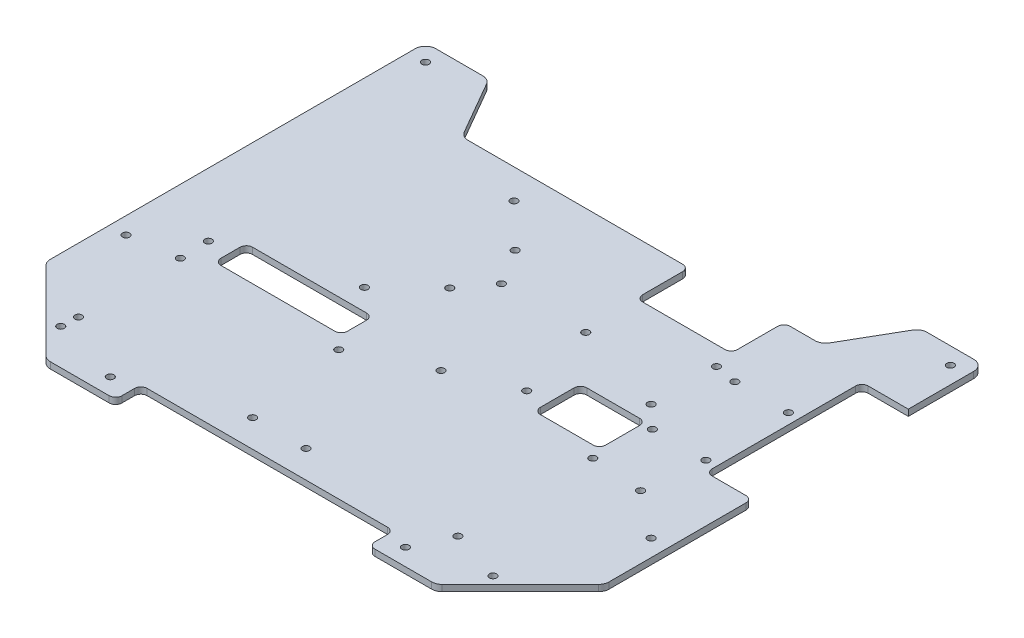
SolidWorks part; units mm, degrees
material "Acier non allié"
ref_plane "Front" through (0, 0, 0) normal (0, 0, 1) x (1, 0, 0)
ref_plane "Top" through (0, 0, 0) normal (0, 1, 0) x (1, 0, 0)
ref_plane "Right" through (0, 0, 0) normal (1, 0, 0) x (0, 0, -1)
sketch "Esquisse1" plane through (0, 0, 0) normal (0, 1, 0) x (1, 0, 0)
  line L0 (0, 0) -> (0, 190) construction
  line L1 (-92.5, 0) -> (92.5, 0)
  line L2 (92.5, 0) -> (132.5, 40)
  line L3 (132.5, 40) -> (132.5, 220)
  line L4 (132.5, 220) -> (102.5, 220)
  line L5 (102.5, 220) -> (85.1795, 190)
  line L6 (85.1795, 190) -> (-85.1795, 190)
  line L7 (-102.5, 220) -> (-85.1795, 190)
  line L8 (-132.5, 220) -> (-102.5, 220)
  line L9 (-132.5, 40) -> (-132.5, 220)
  line L10 (-92.5, 0) -> (-132.5, 40)
  dimension "D1" = 132.5
  dimension "D2" = 220
  dimension "D3" = 60
  dimension "D4" = 30
  dimension "D5" = 40
  dimension "D6" = 40
  dimension "D7" = 30
extrude "Boss.-Extru.1" add sketch "Esquisse1" along normal blind 3
fillet "Congé1" radius 5 10 edges at (92.5, 1.5, 0) (132.5, 1.5, -40) (132.5, 1.5, -220) (102.5, 1.5, -220) (85.1795, 1.5, -190) (-85.1795, 1.5, -190) (-102.5, 1.5, -220) (-132.5, 1.5, -220) (-92.5, 1.5, 0) (-132.5, 1.5, -40)
sketch "Esquisse2" plane through (0, 3, 0) normal (0, 1, 0) x (1, 0, 0)
  line L0 (0, 0) -> (0, 294.1173) construction
  line L2 (-90.4289, 0) -> (90.4289, 0) construction
  circle A0 centre (70, 8) radius 1
  circle A1 centre (124.5, 70) radius 1
  circle A2 centre (124.5, 212) radius 1
  circle A3 centre (-124.5, 212) radius 1
  circle A4 centre (-124.5, 70) radius 1
  circle A5 centre (-70, 8) radius 1
  dimension "D2" = 2
  dimension "D6" = 2
  dimension "D9" = 2
  dimension "D1" = 70
  dimension "D3" = 8
  dimension "D4" = 124.5
  dimension "D5" = 70
  dimension "D7" = 124.5
  dimension "D8" = 212
extrude "Enlèv. mat.-Extru.1" cut sketch "Esquisse2" against normal blind 3
hole_wizard "Dégagement M31" positions "Esquisse3" profile "Esquisse4" hole size "M3" standard "ISO" end condition through all
sketch "Esquisse3" plane through (0, 3, 0) normal (0, 1, 0) x (1, 0, 0)
  point P0 (70, 8)
  point P3 (-70, 8)
  point P6 (-124.5, 70)
  point P9 (-124.5, 212)
  point P12 (124.5, 212)
  point P15 (124.5, 70)
sketch "Esquisse4" plane through (70, 3, -8) normal (1, 0, 0) x (0, 0, 1)
  line L0 (0, 0) -> (0, 3)
  line L1 (0, 3) -> (1.7, 3)
  line L2 (1.7, 3) -> (1.7, 0)
  line L5 (1.7, 0) -> (0, 0)
  line L11 (0, -6.35) -> (0, 107.95) construction
  dimension "Diamètre du perçage jusqu'au prochain" = 3.4
  dimension "Profondeur du perçage jusqu'au prochain" = 3
sketch "Esquisse5" plane through (0, 3, 0) normal (0, 1, 0) x (1, 0, 0)
  line L0 (82.2927, 190) -> (-82.2927, 190) construction
  line L1 (67.5, 190) -> (22.5, 190)
  line L2 (67.5, 190) -> (67.5, 165)
  line L3 (67.5, 165) -> (22.5, 165)
  line L4 (22.5, 190) -> (22.5, 165)
  line L5 (132.5, 42.0711) -> (132.5, 215) construction
  line L6 (132.5, 184) -> (110.5, 184)
  line L7 (132.5, 184) -> (132.5, 110)
  line L8 (132.5, 110) -> (110.5, 110)
  line L9 (110.5, 184) -> (110.5, 110)
  line L10 (127.5, 220) -> (105.3868, 220) construction
  dimension "D1" = 25
  dimension "D2" = 65
  dimension "D3" = 110
  dimension "D4" = 36
  dimension "D5" = 110
  dimension "D6" = 22
extrude "Enlèv. mat.-Extru.2" cut sketch "Esquisse5" against normal through all
fillet "Congé2" radius 3 7 edges at (132.5, 1.5, -110) (110.5, 1.5, -110) (110.5, 1.5, -184) (67.5, 1.5, -190) (67.5, 1.5, -165) (22.5, 1.5, -165) (22.5, 1.5, -190)
sketch "Esquisse6" plane through (0, 3, 0) normal (0, 1, 0) x (1, 0, 0)
  line L0 (110.5, 140.5) -> (-167.6757, 140.5) construction
  line L1 (110.5, 181) -> (110.5, 113) construction
  line L2 (-90.4289, 0) -> (90.4289, 0) construction
  line L3 (110.5, 181) -> (110.5, 113) construction
  circle A0 centre (69.5, 156) radius 1
  circle A1 centre (-26, 156) radius 1
  circle A2 centre (-46.5, 176) radius 1
  circle A3 centre (69.5, 125) radius 1
  circle A4 centre (-26, 125) radius 1
  circle A5 centre (-46.5, 105) radius 1
  dimension "D4" = 2
  dimension "D6" = 2
  dimension "D10" = 2
  dimension "D1" = 140.5
  dimension "D2" = 41
  dimension "D3" = 15.5
  dimension "D5" = 136.5
  dimension "D7" = 15.5
  dimension "D8" = 35.5
  dimension "D9" = 157
extrude "Enlèv. mat.-Extru.3" cut sketch "Esquisse6" against normal through all
hole_wizard "Dégagement M32" positions "Esquisse7" profile "Esquisse8" hole size "M3" standard "ISO"
sketch "Esquisse7" plane through (0, 3, 0) normal (0, 1, 0) x (1, 0, 0)
  point P0 (-46.5, 105)
  point P3 (-26, 125)
  point P6 (-26, 156)
  point P9 (-46.5, 176)
  point P12 (69.5, 156)
  point P15 (69.5, 125)
sketch "Esquisse8" plane through (-46.5, 3, -105) normal (1, 0, 0) x (0, 0, 1)
  line L0 (0, 0) -> (0, 11.0215)
  line L1 (0, 11.0215) -> (1.7, 10)
  line L2 (1.7, 10) -> (1.7, 0)
  line L5 (1.7, 0) -> (0, 0)
  line L10 (0, 11.0215) -> (-1.7, 10) construction
  line L11 (0, -6.35) -> (0, 107.95) construction
  dimension "Diamètre du perçage" = 3.4
  dimension "Profondeur du perçage" = 10
  dimension "Angle de pointe" = 118
sketch "Esquisse9" plane through (0, 3, 0) normal (0, 1, 0) x (1, 0, 0)
  line L0 (132.5, 42.0711) -> (132.5, 107) construction
  line L1 (-90.4289, 0) -> (90.4289, 0) construction
  line L7 (5.84, 25) -> (5.84, 89) construction
  line L8 (25.5, 165) -> (64.5, 165) construction
  line L9 (24.5, 139) -> (-15.5, 139) construction
  line L10 (110.5, 181) -> (110.5, 113) construction
  line L11 (113.5, 110) -> (129.5, 110) construction
  line L12 (-132.5, 215) -> (-132.5, 42.0711) construction
  line L13 (-102.13, 25) -> (-102.13, 73.34) construction
  line L14 (-102.13, 25) -> (-19.5, 25) construction
  line L15 (-102.13, 73.34) -> (-27, 73.34) construction
  circle A0 centre (105.5, 115) radius 1
  circle A3 centre (105.5, 154.12) radius 1
  circle A6 centre (-102.13, 73.34) radius 1
  circle A7 centre (-27, 73.34) radius 1
  circle A8 centre (-19.5, 25) radius 1
  circle A9 centre (-102.13, 25) radius 1
  circle A10 centre (5.84, 89) radius 1
  circle A11 centre (77.84, 89) radius 1
  circle A12 centre (5.84, 25) radius 1
  circle A13 centre (77.84, 25) radius 1
  circle A14 centre (-15.5, 139) radius 1
  circle A15 centre (24.5, 139) radius 1
  circle A16 centre (34.5, 101) radius 1
  circle A17 centre (80.1, 115) radius 1
  circle A18 centre (80.1, 154.12) radius 1
  point P40 (0, 0)
  dimension "D2" = 2
  dimension "D4" = 2
  dimension "D17" = 2
  dimension "D18" = 2
  dimension "D19" = 2
  dimension "D20" = 2
  dimension "D21" = 2
  dimension "D22" = 2
  dimension "D23" = 2
  dimension "D24" = 2
  dimension "D32" = 2
  dimension "D33" = 2
  dimension "D34" = 2
  dimension "D11" = 2
  dimension "D12" = 2
  dimension "D5" = 27
  dimension "25" = 27
  dimension "D10" = 39.12
  dimension "D25" = 72
  dimension "D26" = 72
  dimension "D27" = 64
  dimension "D28" = 64
  dimension "D30" = 25
  dimension "D31" = 25
  dimension "D37" = 40
  dimension "D39" = 10
  dimension "D7" = 5
  dimension "D8" = 25.4
  dimension "D9" = 25.4
  dimension "D40" = 39.12
  dimension "D38" = 76
  dimension "D6" = 38
  dimension "D35" = 26
  dimension "D16" = 113
  dimension "D15" = 82.63
  dimension "D36" = 25
  dimension "D41" = 48.34
  dimension "D13" = 75.13
  dimension "D14" = 54.66
extrude "Enlèv. mat.-Extru.4" cut sketch "Esquisse9" against normal through all
hole_wizard "Dégagement M33" positions "Esquisse10" profile "Esquisse11" hole size "M3" standard "ISO"
sketch "Esquisse10" plane through (0, 3, 0) normal (0, 1, 0) x (1, 0, 0)
  point P3 (105.5, 115)
  point P9 (105.5, 154.12)
  point P14 (80.1, 154.12)
  point P17 (80.1, 115)
sketch "Esquisse11" plane through (105.5, 3, -115) normal (1, 0, 0) x (0, 0, 1)
  line L0 (0, 0) -> (0, 11.0215)
  line L1 (0, 11.0215) -> (1.7, 10)
  line L2 (1.7, 10) -> (1.7, 0)
  line L5 (1.7, 0) -> (0, 0)
  line L10 (0, 11.0215) -> (-1.7, 10) construction
  line L11 (0, -6.35) -> (0, 107.95) construction
  dimension "Diamètre du perçage" = 3.4
  dimension "Profondeur du perçage" = 10
  dimension "Angle de pointe" = 118
sketch "Esquisse12" plane through (0, 3, 0) normal (0, 1, 0) x (1, 0, 0)
  line L2 (-90.4289, 0) -> (90.4289, 0) construction
  line L3 (102.5, 17) -> (-102.5, 17) construction
  line L4 (102.5, 17) -> (102.5, 87) construction
  line L5 (102.5, 87) -> (-102.5, 87) construction
  line L6 (-102.5, 17) -> (-102.5, 87) construction
  line L7 (132.5, 42.0711) -> (132.5, 107) construction
  circle A4 centre (-102.5, 87) radius 1
  circle A5 centre (102.5, 87) radius 1
  circle A6 centre (102.5, 17) radius 1
  circle A7 centre (-102.5, 17) radius 1
  point P6 (102.5, 52)
  dimension "D5" = 2
  dimension "D6" = 2
  dimension "D7" = 2
  dimension "D8" = 2
  dimension "D1" = 70
  dimension "D2" = 205
  dimension "D3" = 17
  dimension "D4" = 30
extrude "Enlèv. mat.-Extru.5" cut sketch "Esquisse12" against normal through all and the other way through all
hole_wizard "Dégagement M34" positions "Esquisse13" profile "Esquisse14" hole size "M3" standard "ISO"
sketch "Esquisse13" plane through (0, 3, 0) normal (0, 1, 0) x (1, 0, 0)
  point P3 (-102.13, 73.34)
  point P6 (-102.13, 25)
  point P9 (-19.5, 25)
  point P12 (-27, 73.34)
  point P16 (5.84, 25)
  point P19 (77.84, 25)
  point P22 (5.84, 89)
  point P25 (77.84, 89)
  point P29 (34.5, 101)
  point P32 (24.5, 139)
  point P35 (-15.5, 139)
sketch "Esquisse14" plane through (-102.13, 3, -73.34) normal (1, 0, 0) x (0, 0, 1)
  line L0 (0, 0) -> (0, 11.0215)
  line L1 (0, 11.0215) -> (1.7, 10)
  line L2 (1.7, 10) -> (1.7, 0)
  line L5 (1.7, 0) -> (0, 0)
  line L10 (0, 11.0215) -> (-1.7, 10) construction
  line L11 (0, -6.35) -> (0, 107.95) construction
  dimension "Diamètre du perçage" = 3.4
  dimension "Profondeur du perçage" = 10
  dimension "Angle de pointe" = 118
hole_wizard "Dégagement M35" positions "Esquisse15" profile "Esquisse16" hole size "M3" standard "ISO"
sketch "Esquisse15" plane through (0, 3, 0) normal (0, 1, 0) x (1, 0, 0)
  point P0 (-102.5, 17)
  point P3 (-102.5, 87)
  point P6 (102.5, 87)
  point P9 (102.5, 17)
sketch "Esquisse16" plane through (-102.5, 3, -17) normal (1, 0, 0) x (0, 0, 1)
  line L0 (0, 0) -> (0, 11.0215)
  line L1 (0, 11.0215) -> (1.7, 10)
  line L2 (1.7, 10) -> (1.7, 0)
  line L5 (1.7, 0) -> (0, 0)
  line L10 (0, 11.0215) -> (-1.7, 10) construction
  line L11 (0, -6.35) -> (0, 107.95) construction
  dimension "Diamètre du perçage" = 3.4
  dimension "Profondeur du perçage" = 10
  dimension "Angle de pointe" = 118
sketch "Esquisse17" plane through (0, 3, 0) normal (0, 1, 0) x (1, 0, 0)
  line L0 (-90.4289, 0) -> (90.4289, 0) construction
  line L1 (-92.5, 95) -> (-32.5, 95)
  line L2 (-92.5, 95) -> (-92.5, 80)
  line L3 (-92.5, 80) -> (-32.5, 80)
  line L4 (-32.5, 95) -> (-32.5, 80)
  line L5 (-132.5, 215) -> (-132.5, 42.0711) construction
  line L6 (132.5, 42.0711) -> (132.5, 107) construction
  line L7 (44.5, 116.5) -> (75.5, 116.5)
  line L8 (44.5, 116.5) -> (44.5, 94.5)
  line L9 (44.5, 94.5) -> (75.5, 94.5)
  line L10 (75.5, 116.5) -> (75.5, 94.5)
  line L11 (82.2927, 190) -> (70.5, 190) construction
  line L13 (-59.5, 12) -> (60.5, 12)
  line L14 (-59.5, 12) -> (-59.5, 0)
  line L15 (-59.5, 0) -> (60.5, 0)
  line L16 (60.5, 12) -> (60.5, 0)
  dimension "D1" = 60
  dimension "D2" = 15
  dimension "D3" = 80
  dimension "D4" = 40
  dimension "D5" = 31
  dimension "D6" = 22
  dimension "D7" = 57
  dimension "D8" = 73.5
  dimension "D9" = 12
  dimension "D11" = 120
  dimension "D12" = 72
extrude "Enlèv. mat.-Extru.6" cut sketch "Esquisse17" against normal up to surface (3 mm away) up to face at (-102.5, 0, -15.3)
fillet "Congé3" radius 3 12 edges at (60.5, 1.5, 0) (60.5, 1.5, -12) (-59.5, 1.5, -12) (-59.5, 1.5, 0) (44.5, 1.5, -116.5) (75.5, 1.5, -116.5) (75.5, 1.5, -94.5) (44.5, 1.5, -94.5) (-92.5, 1.5, -80) (-32.5, 1.5, -80) (-32.5, 1.5, -95) (-92.5, 1.5, -95)
equation "\"WIDTH\"= 300mm'Total width of the robot"
equation "\"LENGTH\"= 220mm'Total length of the robot"
equation "\"CUT_DEPTH\"= 45mm'Depth of the cut on the edges of the plate"
equation "\"Plate_th\"= 3mm'Thickness of the plate"
equation "\"D1\"= \"Plate_th\""
equation "\"D5@Esquisse9\"=\"25@Esquisse9\""
